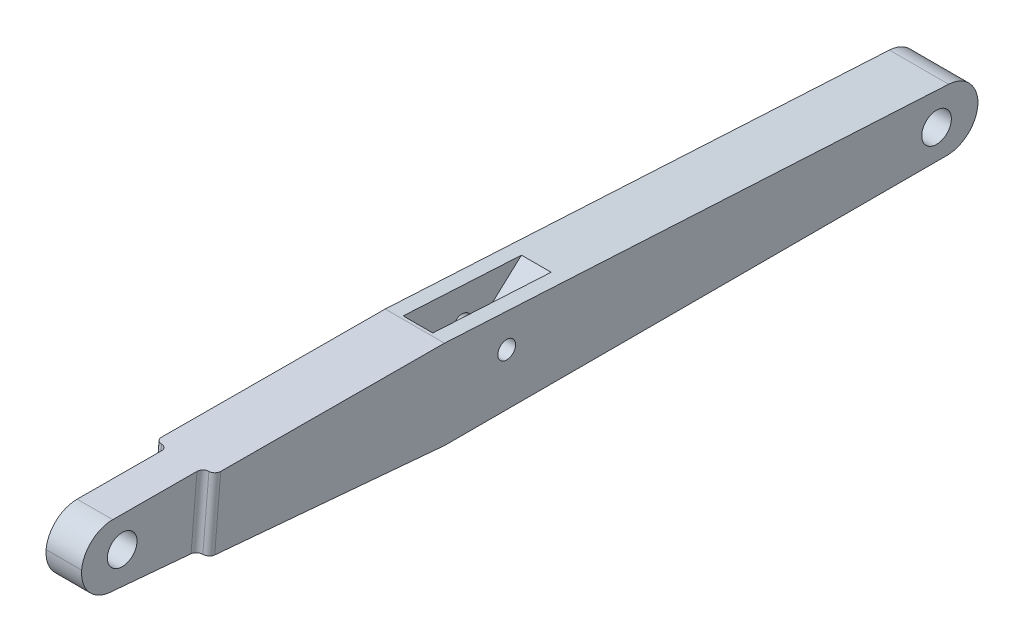
SolidWorks part; units mm, degrees
note: The reader was unsure of these and kept them because the rebuilt part matched: shared geometry of "Sketch6<2>", "Sketch4<3>", "Sketch4<5>", "Sketch4<6>", "Sketch4<7>".
ref_plane "Front Plane" through (0, 0, 0) normal (0, 0, 1) x (1, 0, 0)
ref_plane "Top Plane" through (0, 0, 0) normal (0, 1, 0) x (1, 0, 0)
ref_plane "Right Plane" through (0, 0, 0) normal (1, 0, 0) x (0, 0, -1)
sketch "Sketch2" plane through (0, 0, 0) normal (0, 1, 0) x (1, 0, 0)
  line L1 (-5, 45) -> (5, 45)
  line L2 (-5, 45) -> (-5, -45)
  line L3 (-5, -45) -> (5, -45)
  line L4 (5, 45) -> (5, -45)
  line L5 (-5, 45) -> (5, -45) construction
  line L6 (-5, -45) -> (5, 45) construction
  point P0 (0, 0)
  dimension "D1" = 90
  dimension "D2" = 10
extrude "Boss-Extrude1" add sketch "Sketch2" along normal blind 10
ref_plane "Plane1" through (0, -3.9071, 0.3418) normal (0, -0.9962, 0.0872) x (1, 0, 0)
sketch "Sketch3" plane through (0, -3.9071, 0.3418) normal (0, -0.9962, 0.0872) x (1, 0, 0)
  line L1 (-5, 44.8288) -> (5, 44.8288)
  line L2 (-5, 44.8288) -> (-5, 104.8288)
  line L3 (-5, 104.8288) -> (5, 104.8288)
  line L4 (5, 44.8288) -> (5, 104.8288)
  dimension "D1" = 60
  dimension "D2" = 10
extrude "Boss-Extrude2" add sketch "Sketch3" against normal blind 10
sketch "Sketch4" plane through (5, 0, 0) normal (1, 0, 0) x (0, 0, -1)
  line L1 (45, 10) -> (45, 0) construction
  line L2 (-103.9001, 15.1913) -> (-44.5634, 10)
  line L3 (-44.5634, 10) -> (45, 10)
  line L4 (-103.9001, 15.1913) -> (45, 10) construction
  line L5 (-103.9001, 15.1913) -> (-45.0739, 14.9739)
  line L6 (-44.5634, 14.972) -> (-36.7421, 6.7092)
  line L7 (45, 10) -> (-45.0739, 14.9739)
  line L8 (-24.5634, 13.8413) -> (-32.5403, 6.5563)
  line L9 (-45, 0) -> (45, 0) construction
  line L10 (-103.9001, 15.1913) -> (-104.7717, 5.2293) construction
  circle A0 centre (-97.4675, 10) radius 2.5
  circle A1 centre (-34.5634, 8.7715) radius 3
  circle A2 centre (-34.5634, 8.7715) radius 1.5
  circle A3 centre (38, 5) radius 2.5
  dimension "D1" = 5
  dimension "D2" = 5
  dimension "D3" = 4
  dimension "D7" = 6
  dimension "D8" = 3
  dimension "D9" = 7
  dimension "D4" = 10
  dimension "D5" = 10
  dimension "D6" = 10
  dimension "D10" = 5
  dimension "D11" = 10
  dimension "D12" = 58.8263
extrude "Boss-Extrude3" add sketch "Sketch4" against normal blind 10 contours L3 L7 L5 L2
sketch "Sketch6" plane through (5, 0, 0) normal (1, 0, 0) x (0, 0, -1)
  line L0 (-103.9001, 15.1913) -> (-104.7717, 5.2293)
  line L1 (-104.7717, 5.2293) -> (-84.8478, 3.4862)
  line L2 (-45, 0) -> (-104.7717, 5.2293) construction
  line L3 (-84.8478, 3.4862) -> (-83.8302, 15.1171)
  line L4 (-103.9001, 15.1913) -> (-45.0739, 14.9739) construction
  line L5 (-83.8302, 15.1171) -> (-103.9001, 15.1913)
  dimension "D1" = 20
extrude "Cut-Extrude5" cut sketch "Sketch6" against normal blind 2 from offset 8 offset against normal yes
extrude "Cut-Extrude6" cut sketch "Sketch6<2>" against normal blind 2 contours L5 L0 L1 L3
sketch "Sketch6<2>" plane through (5, 0, 0) normal (1, 0, 0) x (0, 0, -1) same geometry as "Sketch6"
extrude "Cut-Extrude1" cut sketch "Sketch4<3>" against normal blind 10 contours A0
sketch "Sketch4<3>" plane through (5, 0, 0) normal (1, 0, 0) x (0, 0, -1) same geometry as "Sketch4"
extrude "Cut-Extrude2" cut sketch "Sketch4<5>" against normal blind 5 from offset 2.5 offset against normal yes
sketch "Sketch4<5>" plane through (5, 0, 0) normal (1, 0, 0) x (0, 0, -1) same geometry as "Sketch4"
extrude "Cut-Extrude3" cut sketch "Sketch4<6>" against normal through all contours L3 A2 | L3 A2
sketch "Sketch4<6>" plane through (5, 0, 0) normal (1, 0, 0) x (0, 0, -1) same geometry as "Sketch4"
fillet "Fillet3" radius 5.25 2 edges at (0, 5.2293, 104.7717) (0, 15.1913, 103.9001)
fillet "Fillet4" radius 5.25 2 edges at (0, 0, -45) (0, 10, -45)
extrude "Cut-Extrude4" cut sketch "Sketch4<7>" against normal through all contours A3
sketch "Sketch4<7>" plane through (5, 0, 0) normal (1, 0, 0) x (0, 0, -1) same geometry as "Sketch4"
fillet "Fillet5" radius 1 4 edges at (-3, 9.3017, 84.339) (-5, 9.3017, 84.339) (3, 9.3017, 84.339) (5, 9.3017, 84.339)
